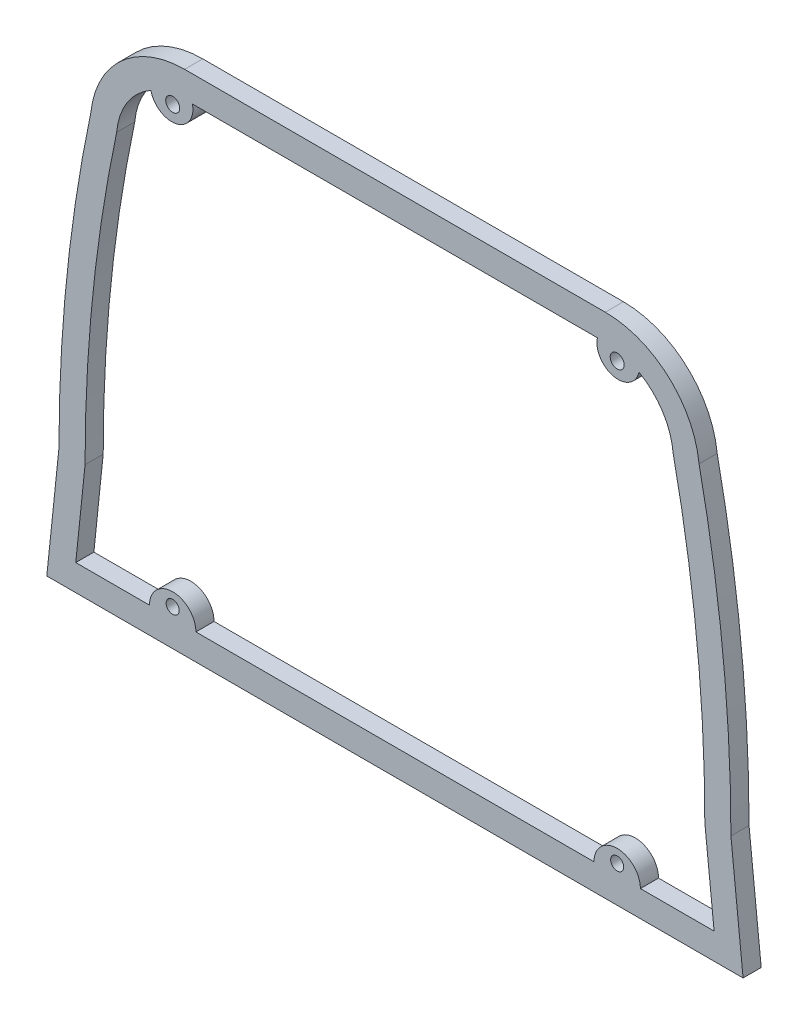
SolidWorks part; units mm, degrees
material "Delrin 2700 NC010, Low Viscosity Acetal Copolymer (SS)"
ref_plane "Front Plane" through (0, 0, 0) normal (0, 0, 1) x (1, 0, 0)
ref_plane "Top Plane" through (0, 0, 0) normal (0, 1, 0) x (1, 0, 0)
ref_plane "Right Plane" through (0, 0, 0) normal (1, 0, 0) x (0, 0, -1)
sketch "Sketch1" plane through (0, 0, 0) normal (0, 0, 1) x (1, 0, 0)
  line L0 (29.4151, -11.9888) -> (30.48, -22.225)
  line L1 (18.415, 22.225) -> (-18.415, 22.225)
  line L2 (-30.48, -22.225) -> (-26.6257, 14.8242) construction
  line L3 (-29.4151, -11.9888) -> (-29.4151, 14.6458) construction
  line L4 (-29.4151, -11.9888) -> (-30.48, -22.225)
  line L5 (18.415, 19.939) -> (-18.415, 19.939)
  line L6 (27.1291, -12.1069) -> (27.9438, -19.939)
  line L7 (-27.9438, -19.939) -> (27.9438, -19.939)
  line L8 (-30.48, -22.225) -> (30.48, -22.225)
  line L9 (-27.1291, -12.1069) -> (-27.9438, -19.939)
  line L18 (0, 18.415) -> (0, -18.415) construction
  line L19 (-1007.9925, 0) -> (48992.0075, 0) construction
  line L24 (-26.797, -2.2098) -> (26.797, -2.2098) construction
  line L25 (-26.797, -2.2098) -> (-26.797, -11.9888) construction
  line L26 (-26.797, -11.9888) -> (26.797, -11.9888) construction
  line L27 (26.797, -2.2098) -> (26.797, -11.9888) construction
  arc A0 (18.415, 22.225) -> (26.6257, 14.8242) centre (18.415, 13.97) cw
  arc A1 (-18.415, 22.225) -> (-26.6257, 14.8242) centre (-18.415, 13.97) ccw
  arc A2 (29.4151, -11.9888) -> (26.6257, 14.8242) centre (-100.8481, -11.9888) ccw
  circle A3 centre (0, -15.748) radius 3.7592 construction
  circle A4 centre (19.4575, -19.05) radius 0.5715
  arc A5 (-29.4151, -11.9888) -> (-26.6257, 14.8242) centre (100.8481, -11.9888) cw
  arc A6 (-27.1291, -12.1069) -> (-24.3623, 14.4786) centre (100.8481, -11.9888) cw
  arc A7 (-21.3655, 19.1588) -> (-17.7253, 19.939) centre (-19.5454, 19.5489) ccw
  arc A8 (21.3655, 19.1588) -> (17.7253, 19.939) centre (19.5454, 19.5489) cw
  circle A9 centre (-19.4575, 19.05) radius 0.6096
  circle A10 centre (19.4575, 19.05) radius 0.6096
  arc A11 (-21.4895, -19.939) -> (-17.4255, -19.939) centre (-19.4575, -19.939) cw
  circle A12 centre (-19.4575, -19.05) radius 0.5715
  arc A13 (21.4895, -19.939) -> (17.4255, -19.939) centre (19.4575, -19.939) ccw
  arc A18 (-18.415, 19.939) -> (-24.3623, 14.4786) centre (-18.415, 13.97) ccw
  arc A19 (18.415, 19.939) -> (24.3623, 14.4786) centre (18.415, 13.97) cw
  arc A20 (27.1291, -12.1069) -> (24.3623, 14.4786) centre (-100.8481, -11.9888) ccw
  point P0 (0, 0)
  point P1 (0, 22.225)
  point P26 (0, -22.225)
  point P31 (0, -11.9888)
  dimension "D4" = 2.286
  dimension "D6" = 8.255
  dimension "D7" = 19.4575
  dimension "D8" = 44.45
  dimension "D9" = 15.748
  dimension "D5" = 1.2192
  dimension "D17" = 1.143
  dimension "D3" = 7.5184
  dimension "D18" = 2.032
  dimension "D2" = 36.83
  dimension "D10" = 19.05
  dimension "D11" = 19.05
  dimension "D12" = 60.96
  dimension "D13" = 19.4575
  dimension "D14" = 22.225
  dimension "D15" = 53.594
  dimension "D16" = 9.779
extrude "Boss-Extrude1" add sketch "Sketch1" along normal blind 1.5875 contours L8 A12 A4 L0 A2 A0 L1 A1 A5 L4 A20 L6 L7 L9 A6 A18 L5 A19 | L5 A18 A7 A9 | A19 L5 A8 A10 | A11 L7 A12 | L7 A13 A4 region at (29.1972, -17.185, 0) region at (19.9299, 19.6989, 0) region at (-19.1643, 17.771, 0) region at (19.4575, -19.8936, 0) region at (-19.4575, -17.9524, 0)
ref_axis "Axis1" through (0, -15.748, 0) along (0, 0, 1)
